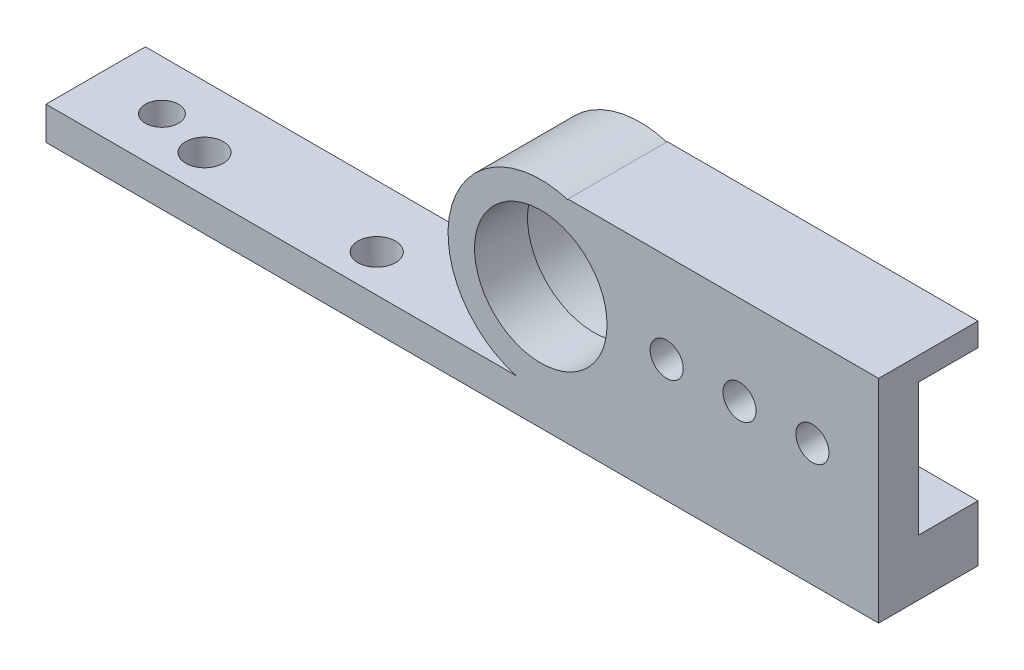
SolidWorks part; units mm, degrees
ref_plane "前视基准面" through (0, 0, 0) normal (0, 0, 1) x (1, 0, 0)
ref_plane "上视基准面" through (0, 0, 0) normal (0, 1, 0) x (1, 0, 0)
ref_plane "右视基准面" through (0, 0, 0) normal (1, 0, 0) x (0, 0, -1)
sketch "草图1" plane through (0, 0, 0) normal (0, 0, 1) x (1, 0, 0)
  line L1 (20, -10) -> (-20, -10)
  line L2 (20, -10) -> (20, 10)
  line L3 (20, 10) -> (-20, 10)
  line L4 (-20, -10) -> (-20, 10)
  line L5 (20, -10) -> (-20, 10) construction
  line L6 (20, 10) -> (-20, -10) construction
  point P0 (0, 0)
  dimension "D1" = 40
  dimension "D2" = 20
extrude "凸台-拉伸1" add sketch "草图1" along normal blind 6
sketch "草图2" plane through (0, 0, 6) normal (0, 0, 1) x (1, 0, 0)
  line L0 (20, -10) -> (20, 10) construction
  circle A0 centre (10, 0) radius 2.5
  circle A1 centre (-1, 0) radius 2.5
  circle A2 centre (-12, 0) radius 2.5
  dimension "D1" = 10
  dimension "D2" = 5
  dimension "D3" = 3
extrude "切除-拉伸1" cut sketch "草图2" against normal through all
sketch "草图3" plane through (0, 0, 6) normal (0, 0, 1) x (1, 0, 0)
  line L0 (20, 13.5) -> (20, 10)
  line L1 (20, -13.5) -> (-26.894, -13.5)
  line L3 (20, 13.5) -> (-26.894, 13.5)
  line L4 (-20, 10) -> (-20, -10)
  line L5 (-20, -10) -> (20, -10)
  line L6 (20, -10) -> (20, 10)
  line L7 (20, 10) -> (-20, 10)
  line L8 (-20, 10) -> (-20, -10)
  line L9 (-20, -10) -> (20, -10)
  line L10 (20, -10) -> (20, 10)
  line L11 (20, 10) -> (-20, 10)
  line L12 (-26.894, -13.5) -> (-26.894, 13.5)
  line L13 (20, -10.0394) -> (-26.894, 13.5) construction
  line L14 (20, 10.0394) -> (-26.894, -13.5) construction
  line L15 (20, -10) -> (20, -13.5)
  circle A0 centre (-31, 0) radius 11
  circle A1 centre (-31, 0) radius 14
  point P2 (0, 0)
  line M10 (-20, 10) -> (-20, -10)
  line M11 (-20, -10) -> (20, -10)
  line M13 (20, 10) -> (-20, 10)
  dimension "D3" = 22
  dimension "D4" = 28
  dimension "D2" = 3.5
  dimension "D1" = 0
extrude "凸台-拉伸2" add sketch "草图3" against normal blind 15 contours L3 A1 L1 L12 A0 | A1 L1 L15 M11 M10 | L1 A1 L8 A0 L12 | L8 A1 L3 L12 A0 | L8 A1 | A1 L0 L3 M10 M13 region at (-1.9449, 11.7771, 6) region at (-1.9449, -11.7771, 6) region at (-23.0173, 9.0328, 6) region at (-27.2274, 11.7946, 6) region at (-18.7882, 0, 6) region at (-23.0173, -9.0328, 6)
sketch "草图5" plane through (0, 0, 6) normal (0, 0, 1) x (1, 0, 0)
  circle A0 centre (-31, 0) radius 10
  circle A1 centre (-31, 0) radius 11 construction
  circle A2 centre (-31, 0) radius 11
  dimension "D1" = 20
extrude "凸台-拉伸3" add sketch "草图5" against normal blind 8
sketch "草图6" plane through (0, 0, 6) normal (0, 0, 1) x (1, 0, 0)
  circle A0 centre (-31, 0) radius 8.5
  circle A1 centre (-31, 0) radius 10 construction
  circle A2 centre (-31, 0) radius 10
  dimension "D1" = 17
sketch "草图9" plane through (0, -13.5, 0) normal (0, -1, 0) x (1, 0, 0)
  circle A0 centre (-18.2368, -1.344) radius 5.5352
sketch "草图10" plane through (20, 0, 0) normal (1, 0, 0) x (0, 0, -1)
  line L1 (9, -13.5) -> (-6, -13.5)
  line L2 (9, -13.5) -> (9, -18.5)
  line L3 (9, -18.5) -> (-6, -18.5)
  line L4 (-6, -13.5) -> (-6, -18.5)
  dimension "D1" = 5
extrude "凸台-拉伸4" add sketch "草图10" against normal blind 200
sketch "草图11" plane through (0, 0, 6) normal (0, 0, 1) x (1, 0, 0)
  line L1 (-28.6193, -11.8661) -> (-25.5243, -11.8661)
  line L2 (-28.6193, -11.8661) -> (-28.6193, -14.961)
  line L3 (-28.6193, -14.961) -> (-25.5243, -14.961)
  line L4 (-25.5243, -11.8661) -> (-25.5243, -14.961)
extrude "凸台-拉伸5" add sketch "草图11" against normal through all
sketch "草图13" plane through (0, -18.5, 0) normal (0, -1, 0) x (1, 0, 0)
  line L0 (-164.0842, 6) -> (-164.0842, -9)
  line L1 (-180, 6) -> (20, 6) construction
  line L2 (-164.0842, 123.2983) -> (-164.0842, -246.7017) construction
  line L3 (-180, -9) -> (20, -9) construction
sketch "草图14" plane through (0, -18.5, 0) normal (0, -1, 0) x (1, 0, 0)
  line L0 (-105.6913, -15.7251) -> (-105.6913, 9.3691)
  line L1 (-105.6913, 230.4998) -> (-105.6913, -139.5002) construction
sketch "草图15" plane through (0, -18.5, 0) normal (0, -1, 0) x (1, 0, 0)
  line L1 (-105.6913, -15.7251) -> (-184.1416, -15.7251)
  line L2 (-105.6913, -15.7251) -> (-105.6913, 11.9644)
  line L3 (-105.6913, 11.9644) -> (-184.1416, 11.9644)
  line L4 (-184.1416, -15.7251) -> (-184.1416, 11.9644)
sketch "草图16" plane through (0, -18.5, 0) normal (0, -1, 0) x (1, 0, 0)
  line L0 (-105.6913, -17.1171) -> (-105.6913, 37.1771)
  line L1 (-105.6913, 230.4998) -> (-105.6913, -139.5002) construction
sketch "草图17" plane through (0, -18.5, 0) normal (0, -1, 0) x (1, 0, 0)
  line L1 (-105.6913, -17.1171) -> (-191.9094, -17.1171)
  line L2 (-105.6913, -17.1171) -> (-105.6913, 25.2398)
  line L3 (-105.6913, 25.2398) -> (-191.9094, 25.2398)
  line L4 (-191.9094, -17.1171) -> (-191.9094, 25.2398)
extrude "切除-拉伸2" cut sketch "草图17" against normal through all
sketch "草图18" plane through (0, -18.5, 0) normal (0, -1, 0) x (1, 0, 0)
  line L0 (-105.6913, 6) -> (-105.6913, -9)
  line L1 (-105.6913, -1.5) -> (-95.6913, -1.5)
  circle A0 centre (-95.6913, -1.5) radius 2.5
  dimension "D2" = 5
  dimension "D1" = 10
extrude "切除-拉伸3" cut sketch "草图18" against normal blind 10 contours A0 region at (-95.6913, -18.5, -3.9293)
sketch "草图19" plane through (0, -18.5, 0) normal (0, -1, 0) x (1, 0, 0)
  circle A0 centre (-87.421, 0.3438) radius 2.8371
  circle A1 centre (-61.421, 0.3438) radius 2.8371
sketch "草图20" plane through (0, -18.5, 0) normal (0, -1, 0) x (1, 0, 0)
  circle A0 centre (-61.421, 0.3438) radius 2.8371 construction
  circle A1 centre (-87.421, 0.3438) radius 2.8371 construction
  circle A2 centre (-61.421, 0.3438) radius 2.8371
  circle A3 centre (-87.421, 0.3438) radius 2.8371
extrude "切除-拉伸4" cut sketch "草图20" against normal blind 10
